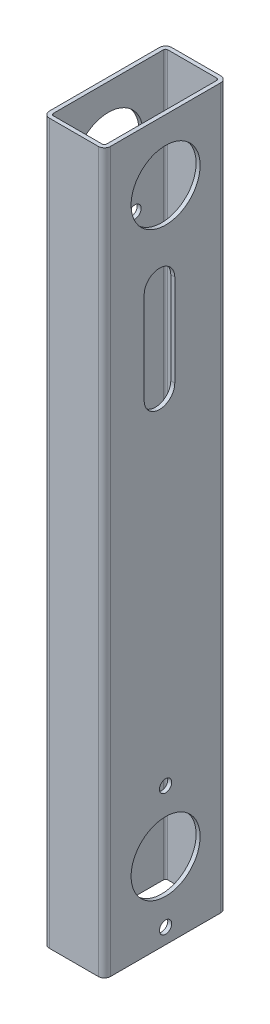
SolidWorks part; units mm, degrees
material "6061-T6 (SS)"
ref_plane "Front Plane" through (0, 0, 0) normal (0, 0, 1) x (1, 0, 0)
ref_plane "Top Plane" through (0, 0, 0) normal (0, 1, 0) x (1, 0, 0)
ref_plane "Right Plane" through (0, 0, 0) normal (1, 0, 0) x (0, 0, -1)
sketch "Sketch1" plane through (0, 0, 0) normal (0, 1, 0) x (1, 0, 0)
  line L1 (10.16, -25.4) -> (-10.16, -25.4)
  line L2 (12.7, -22.86) -> (12.7, 22.86)
  line L3 (10.16, 25.4) -> (-10.16, 25.4)
  line L4 (-12.7, -22.86) -> (-12.7, 22.86)
  line L5 (12.7, -25.4) -> (-12.7, 25.4) construction
  line L6 (12.7, 25.4) -> (-12.7, -25.4) construction
  arc A0 (-10.16, -25.4) -> (-12.7, -22.86) centre (-10.16, -22.86) cw
  arc A1 (10.16, -25.4) -> (12.7, -22.86) centre (10.16, -22.86) ccw
  arc A2 (12.7, 22.86) -> (10.16, 25.4) centre (10.16, 22.86) ccw
  arc A3 (-10.16, 25.4) -> (-12.7, 22.86) centre (-10.16, 22.86) ccw
  point P0 (0, 0)
  dimension "D3" = 2.54
  dimension "D1" = 25.4
  dimension "D2" = 50.8
extrude "Extrude-Thin1" add sketch "Sketch1" along normal blind 222.25 and the other way blind 76.2 thin thin type one direction reverse wall 1.651
sketch "Sketch2" plane through (-12.7, 0, 0) normal (-1, 0, 0) x (0, 0, 1)
  line L0 (2.54, 161.9426) -> (2.54, 12.7) construction
  line L4 (9.2075, 161.9426) -> (9.2075, 12.7)
  line L5 (-4.1275, 161.9426) -> (-4.1275, 12.7)
  line L6 (2.54, 25.4) -> (2.54, 149.2426) construction
  arc A2 (9.2075, 161.9426) -> (-4.1275, 161.9426) centre (2.54, 161.9426) ccw
  arc A3 (-4.1275, 12.7) -> (9.2075, 12.7) centre (2.54, 12.7) ccw
  point P3 (2.54, 87.3213)
  dimension "D5" = 13.335
  dimension "D2" = 12.7
  dimension "D1" = 12.7
extrude "Cut-Extrude1" cut sketch "Sketch2" against normal up to next
sketch "Sketch5" plane through (12.7, 0, 0) normal (1, 0, 0) x (0, 0, -1)
  line L0 (-2.54, 161.9426) -> (-2.54, 123.8426) construction
  line L1 (3.81, 161.9426) -> (3.81, 123.8426)
  line L2 (-8.89, 161.9426) -> (-8.89, 123.8426)
  arc A0 (3.81, 161.9426) -> (-8.89, 161.9426) centre (-2.54, 161.9426) ccw
  arc A1 (-8.89, 123.8426) -> (3.81, 123.8426) centre (-2.54, 123.8426) ccw
  arc A2 (4.1275, 161.9426) -> (-9.2075, 161.9426) centre (-2.54, 161.9426) ccw construction
  point P2 (-2.54, 142.8926)
  dimension "D1" = 6.35
  dimension "D2" = 38.1
extrude "Cut-Extrude4" cut sketch "Sketch5" against normal up to next
sketch "Sketch4" plane through (-12.7, 0, 0) normal (1, 0, 0) x (0, 0, -1)
  circle A12 centre (11.049, 4.7713) radius 2.5527
  circle A13 centre (-16.129, 4.7713) radius 2.5527
  circle A14 centre (-16.129, 87.3213) radius 2.5527
  circle A15 centre (11.049, 87.3213) radius 2.5527
  circle A16 centre (-16.129, 169.8713) radius 2.5527
  circle A17 centre (11.049, 169.8713) radius 2.5527
  dimension "D1" = 5.1054
extrude "Cut-Extrude3" cut sketch "Sketch4" along normal up to surface (1.651 mm away) up to face at (-11.049, 87.3213, 2.54)
sketch "Sketch6" plane through (12.7, 0, 0) normal (1, 0, 0) x (0, 0, -1)
  line L0 (25.4, -76.2) -> (25.4, 222.25) construction
  circle A0 centre (0, -44.45) radius 14.3256
  circle A1 centre (0, 196.85) radius 14.3256
  dimension "D1" = 28.6512
  dimension "D2" = 25.4
  dimension "D3" = 44.45
  dimension "D4" = 241.3
extrude "Cut-Extrude5" cut sketch "Sketch6" against normal through all
hole_wizard "#10 Clearance Hole1" positions "Sketch8" profile "Sketch9" hole size "#10" standard "ANSI Inch" end condition through all
sketch "Sketch8" plane through (12.7, 0, 0) normal (1, 0, 0) x (0, 0, -1)
  circle A0 centre (0, -44.45) radius 25.4 construction
  point P0 (0, -19.05)
  point P11 (0, -69.85)
  dimension "D1" = 50.8
sketch "Sketch9" plane through (12.7, -19.05, 0) normal (0, 1, 0) x (0, 0, -1)
  line L0 (0, 0) -> (0, 25.4)
  line L1 (0, 25.4) -> (2.5527, 25.4)
  line L2 (2.5527, 25.4) -> (2.5527, 0)
  line L5 (2.5527, 0) -> (0, 0)
  line L11 (0, -6.35) -> (0, 107.95) construction
  dimension "Thru Hole Dia." = 5.1054
  dimension "Thru Hole Depth" = 25.4
